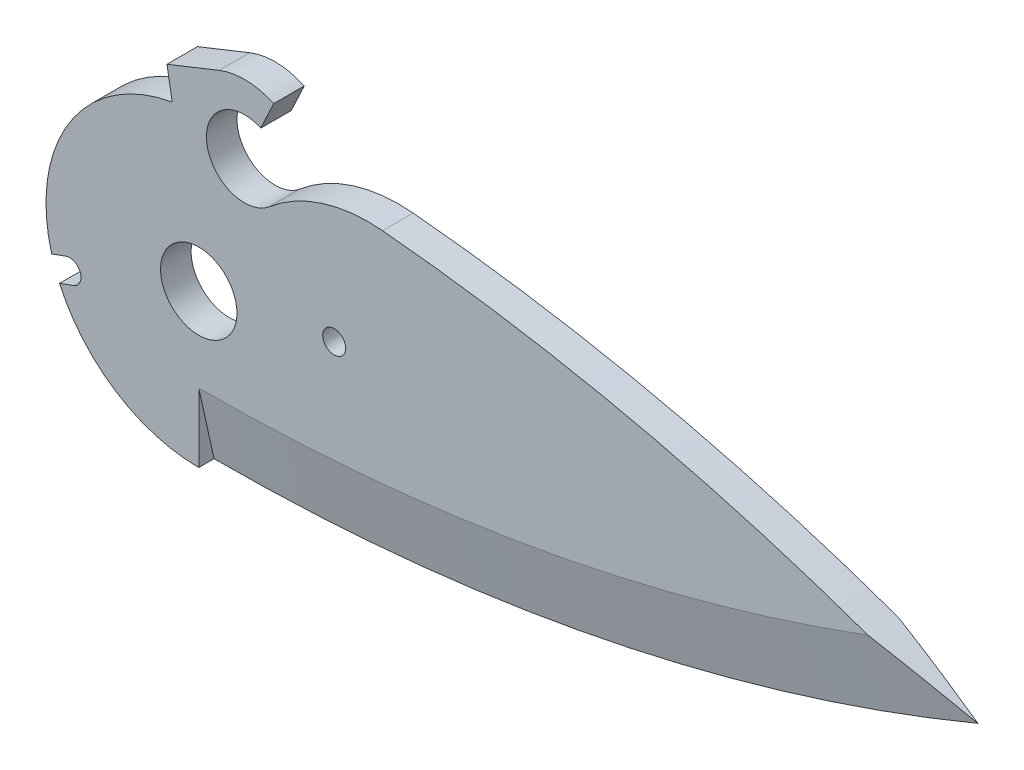
SolidWorks part; units mm, degrees
material "AISI Typ A2 Nástrojová ocel"
ref_plane "Přední rovina" through (0, 0, 0) normal (0, 0, 1) x (1, 0, 0)
ref_plane "Horní rovina" through (0, 0, 0) normal (0, 1, 0) x (1, 0, 0)
ref_plane "Pravá rovina" through (0, 0, 0) normal (1, 0, 0) x (0, 0, -1)
sketch "Skica1" plane through (0, 0, 0) normal (0, 0, 1) x (1, 0, 0)
  line L0 (0, 0) -> (28.9614, 0) construction
  line L1 (1.3336, 13.1801) -> (-2.0838, 11.8177)
  line L2 (-2.0838, 11.8177) -> (-1.7365, 9.8481)
  line L3 (0, 10) -> (0, -10) construction
  line L4 (3, 9) -> (3, 16.5233) construction
  line L5 (4.0565, 11.2658) -> (4.9018, 13.0784)
  line L7 (0, 0) -> (58.3677, 0) construction
  line L8 (0, 0) -> (-0.0542, 0.0512) construction
  circle A0 centre (0, 0) radius 2.5
  arc A1 (-1.7365, 9.8481) -> (-10, 0) centre (0, 0) ccw
  arc A2 (12.0319, 9.442) -> (50, 0) centre (0, -120) cw
  arc A3 (0, -10) -> (50, 0) centre (0, 120) ccw
  arc A4 (4.0565, 11.2658) -> (4.6213, 7.097) centre (3, 9) ccw
  arc A5 (12.0319, 9.442) -> (4.6213, 7.097) centre (11.1064, -0.5151) ccw
  arc A6 (4.9018, 13.0784) -> (1.3336, 13.1801) centre (3, 9) ccw
  arc A9 (-10, 0) -> (0, -10) centre (0, 0) ccw
  dimension "D1" = 10
  dimension "D2" = 5
  dimension "D3" = 60
  dimension "D5" = 2.5
  dimension "D6" = 2
  dimension "D8" = 10
  dimension "D11" = 10
  dimension "D12" = 0
  dimension "D4" = 3
  dimension "D7" = 25
  dimension "D9" = 2
  dimension "D10" = 9
extrude "Přidat vysunutím1" add sketch "Skica1" along normal mid plane 2
sketch "Skica4" plane through (0, 0, 0) normal (0, 0, 1) x (1, 0, 0)
  line L0 (0, 0) -> (8.8633, 1.5628) construction
  line L1 (0, 0) -> (27.9086, 0) construction
  line L2 (0, 0) -> (-8.4572, -3.0782) construction
  line L3 (-2.0838, 11.8177) -> (-1.7365, 9.8481) construction
  line L4 (-8.7137, -2.3734) -> (-9.627, -2.7058)
  line L5 (-8.2007, -3.783) -> (-9.1139, -4.1153)
  circle A0 centre (8.8633, 1.5628) radius 0.75
  arc A1 (-8.2007, -3.783) -> (-8.7137, -2.3734) centre (-8.4572, -3.0782) ccw
  arc A2 (-1.7365, 9.8481) -> (0, -10) centre (0, 0) ccw construction
  arc A3 (-9.627, -2.7058) -> (-9.1139, -4.1153) centre (0, 0) ccw
  dimension "D2" = 1.5
  dimension "D1" = 9
  dimension "D3" = 10
  dimension "D4" = 100
extrude "Odebrat vysunutím1" cut sketch "Skica4" against normal through all and the other way through all
sketch "Skica2" plane through (0, 0, 0) normal (1, 0, 0) x (0, 0, -1)
  line L0 (0, -10) -> (1, -5.4893)
  line L1 (-1, -10) -> (1, -10) construction
  line L2 (1, -2.7058) -> (1, 9.8481) construction
  line L3 (0, -10) -> (0, -2.6677) construction
  line L4 (0, -10) -> (-1, -5.4893)
  line L5 (-1, -5.4893) -> (-1, -10)
  line L6 (-1, -10) -> (0, -10)
  line L7 (1, -5.4893) -> (1, -10)
  line L8 (1, -10) -> (0, -10)
  line L9 (0, -10) -> (0.0115, -9.9693)
  dimension "D1" = 25
sketch "Skica3" plane through (0, 0, 0) normal (0, 0, 1) x (1, 0, 0)
  arc A0 (0, -10) -> (50, 0) centre (0, 120) ccw construction
  arc A1 (0, -10) -> (50, 0) centre (0, 120) ccw
sweep "Odebrat tažením po křivce1" cut profiles "Skica2" path "Skica3"
mirror "Zrcadlit1" about plane through (0, 0, 0) normal (0, 0, 1) of "Odebrat tažením po křivce1"
sketch "Skica5" plane through (0, 0, -1) normal (0, 0, -1) x (-1, 0, 0)
  circle A0 centre (-13.6099, 7.7362) radius 0.9715
extrude "Přidat vysunutím2" [suppressed] add sketch "Skica5" along normal blind 2
